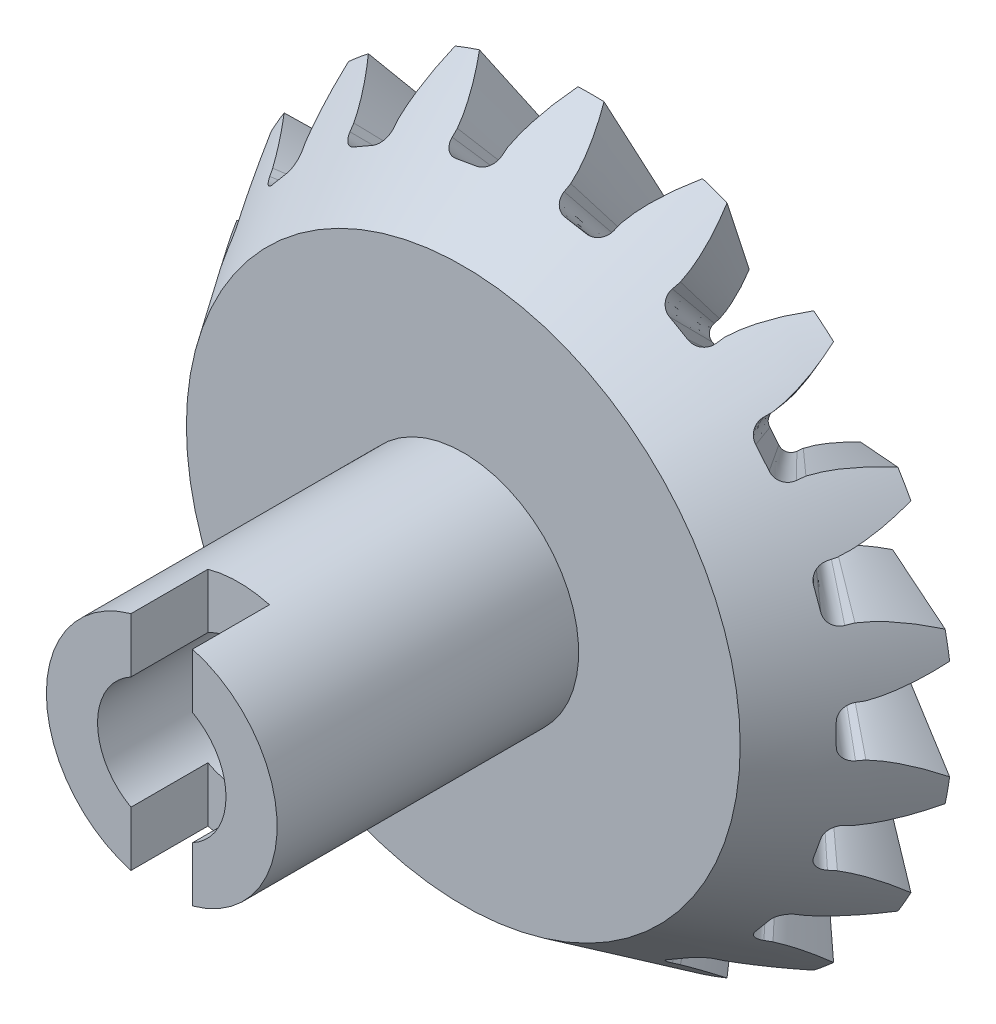
SolidWorks part; units mm, degrees
ref_plane "Front Plane" through (0, 0, 0) normal (0, 0, 1) x (1, 0, 0)
ref_plane "Top Plane" through (0, 0, 0) normal (0, 1, 0) x (1, 0, 0)
ref_plane "Right Plane" through (0, 0, 0) normal (1, 0, 0) x (0, 0, -1)
ref_axis "Gear Axis" through (0, 0, -1.3521) along (0, 0, 1)
sketch "Blank Sketch" plane through (0, 0, 0) normal (0, 1, 0) x (1, 0, 0)
  line L0 (0, 0) -> (0, -27.0416) construction
  line L1 (0, 0) -> (22.5, -15) construction
  line L2 (0, 0) -> (15.0115, -10.0077) construction
  line L3 (11.176, -15.7611) -> (15.6135, -9.1047)
  line L4 (15.6135, -9.1047) -> (23.5324, -13.4515)
  line L5 (23.5324, -13.4515) -> (17.9981, -21.7528)
  line L6 (17.9981, -21.7528) -> (4.175, -21.7528)
  line L7 (4.175, -21.7528) -> (4.175, -15.7611)
  line L8 (4.175, -15.7611) -> (11.176, -15.7611)
  line L9 (22.5, -15) -> (23.5324, -13.4515) construction
  line L10 (22.5, -15) -> (17.9981, -21.7528) construction
  line L11 (15.0115, -10.0077) -> (11.176, -15.7611) construction
  dimension "Axis" = 27.0416
  dimension "Cone" = 56.31
  dimension "Heel" = 27.0416
  dimension "Toe Cone" = 56.31
  dimension "Toe" = 18.0416
  dimension "Heel Square" = 90
  dimension "Addendum" = 1.8611
  dimension "Root Square" = 90
  dimension "Heel Rim" = 8.1158
  dimension "Toe Square" = 90
  dimension "Toe Rim" = 6.9147
  dimension "Front Square" = 90
  dimension "Face" = 4.927
  dimension "Back" = 13.8231
  dimension "Front" = 7.001
revolve "Blank" add sketch "Blank Sketch" angle 360 about L0
sketch "Cone Sketch" plane through (0, 0, 0) normal (0, 1, 0) x (1, 0, 0)
  line L0 (0, 0) -> (0, -27.0416) construction
  line L1 (0, 0) -> (24.5801, -16.3868)
  line L2 (0, 0) -> (12.9314, -8.6209)
  dimension "Axis" = 27.0416
  dimension "Toe Cone" = 56.31
  dimension "Heel Cone" = 56.31
  dimension "Heel" = 29.5416
  dimension "Toe" = 15.5416
ref_plane "Heel Plane" through (24.5801, 0, 16.3868) normal (0.8321, 0, 0.5547) x (0.5547, 0, -0.8321)
ref_plane "Toe Plane" through (12.9314, 0, 8.6209) normal (0.8321, 0, 0.5547) x (0.5547, 0, -0.8321)
sketch "Heel Section Sketch" plane through (24.5801, 0, 16.3868) normal (0.8321, 0, 0.5547) x (0.5547, 0, -0.8321)
  line L0 (0, 0) -> (-44.3125, 0) construction
  line L1 (-2.4254, 1.822) -> (-2.9568, 1.7989)
  line L2 (-2.4254, -1.822) -> (-2.9568, -1.7989)
  line L3 (4.4731, 5.3382) -> (4.4731, -5.3382)
  arc A0 (-2.9568, 1.7989) -> (-3.9494, 0.7429) centre (-2.9117, 0.762) ccw
  arc A1 (-3.9494, -0.7429) -> (-2.9568, -1.7989) centre (-2.9117, -0.762) ccw
  arc A2 (-3.9494, -0.7429) -> (-3.9494, 0.7429) centre (-44.3125, 0) ccw
  spline S0 degree 4 poles (-2.6185, 1.7952) (-2.5735, 1.8001) (-2.4634, 1.8153) (-2.3826, 1.8283) (-2.1666, 1.8686) (-2.0036, 1.9057) (-1.7812, 1.9593) (-1.5664, 2.0195) (-1.329, 2.0902) (-1.1027, 2.1645) (-0.8722, 2.2444) (-0.6468, 2.3281) (-0.412, 2.4198) (-0.1247, 2.538) (0.217, 2.6881) (0.607, 2.871) (1.0408, 3.0905) (1.4634, 3.3174) (1.8882, 3.5612) (2.2942, 3.8046) (2.7157, 4.0742) (3.0965, 4.325) (3.5292, 4.6295) (3.8609, 4.867) (4.3217, 5.2186) (4.5362, 5.3868) (4.8006, 5.5995) (4.951, 5.7231) (5.0219, 5.782) (5.0608, 5.8144) (5.0806, 5.831) knots 0 0 0 0 0 0.022117 0.039787 0.058126 0.081614 0.109122 0.13663 0.164138 0.191645 0.219153 0.246661 0.274169 0.305931 0.360947 0.415962 0.470978 0.525993 0.581009 0.636024 0.69104 0.746055 0.801071 0.856086 0.911102 0.955551 0.977775 0.988888 1 1 1 1 1 construction
  spline S1 degree 4 poles (-2.4254, 1.822) (-2.3913, 1.8275) (-2.324, 1.8392) (-2.1666, 1.8686) (-2.0036, 1.9057) (-1.7812, 1.9593) (-1.5664, 2.0195) (-1.329, 2.0902) (-1.1027, 2.1645) (-0.8722, 2.2444) (-0.6468, 2.3281) (-0.412, 2.4198) (-0.1247, 2.538) (0.217, 2.6881) (0.607, 2.871) (1.0408, 3.0905) (1.4634, 3.3174) (1.8882, 3.5612) (2.2942, 3.8046) (2.7157, 4.0742) (3.0965, 4.325) (3.5292, 4.6295) (3.8609, 4.867) (4.2239, 5.144) (4.3887, 5.2717) (4.4731, 5.3382) knots 0.022117 0.022117 0.022117 0.022117 0.022117 0.039787 0.058126 0.081614 0.109122 0.13663 0.164138 0.191645 0.219153 0.246661 0.274169 0.305931 0.360947 0.415962 0.470978 0.525993 0.581009 0.636024 0.69104 0.746055 0.801071 0.856086 0.911102 0.911102 0.911102 0.911102 0.911102
  spline S2 degree 4 poles (-2.6185, -1.7952) (-2.5735, -1.8001) (-2.4634, -1.8153) (-2.3826, -1.8283) (-2.1666, -1.8686) (-2.0036, -1.9057) (-1.7812, -1.9593) (-1.5664, -2.0195) (-1.329, -2.0902) (-1.1027, -2.1645) (-0.8722, -2.2444) (-0.6468, -2.3281) (-0.412, -2.4198) (-0.1247, -2.538) (0.217, -2.6881) (0.607, -2.871) (1.0408, -3.0905) (1.4634, -3.3174) (1.8882, -3.5612) (2.2942, -3.8046) (2.7157, -4.0742) (3.0965, -4.325) (3.5292, -4.6295) (3.8609, -4.867) (4.3217, -5.2186) (4.5362, -5.3868) (4.8006, -5.5995) (4.951, -5.7231) (5.0219, -5.782) (5.0608, -5.8144) (5.0806, -5.831) knots 0 0 0 0 0 0.022117 0.039787 0.058126 0.081614 0.109122 0.13663 0.164138 0.191645 0.219153 0.246661 0.274169 0.305931 0.360947 0.415962 0.470978 0.525993 0.581009 0.636024 0.69104 0.746055 0.801071 0.856086 0.911102 0.955551 0.977775 0.988888 1 1 1 1 1 construction
  spline S3 degree 4 poles (-2.4254, -1.822) (-2.3913, -1.8275) (-2.324, -1.8392) (-2.1666, -1.8686) (-2.0036, -1.9057) (-1.7812, -1.9593) (-1.5664, -2.0195) (-1.329, -2.0902) (-1.1027, -2.1645) (-0.8722, -2.2444) (-0.6468, -2.3281) (-0.412, -2.4198) (-0.1247, -2.538) (0.217, -2.6881) (0.607, -2.871) (1.0408, -3.0905) (1.4634, -3.3174) (1.8882, -3.5612) (2.2942, -3.8046) (2.7157, -4.0742) (3.0965, -4.325) (3.5292, -4.6295) (3.8609, -4.867) (4.2239, -5.144) (4.3887, -5.2717) (4.4731, -5.3382) knots 0.022117 0.022117 0.022117 0.022117 0.022117 0.039787 0.058126 0.081614 0.109122 0.13663 0.164138 0.191645 0.219153 0.246661 0.274169 0.305931 0.360947 0.415962 0.470978 0.525993 0.581009 0.636024 0.69104 0.746055 0.801071 0.856086 0.911102 0.911102 0.911102 0.911102 0.911102
  dimension "Root" = 40.3699
  dimension "Fillet" = 1.0378
  dimension "Centre" = 44.3125
sketch "Toe Section Sketch" plane through (12.9314, 0, 8.6209) normal (0.8321, 0, 0.5547) x (0.5547, 0, -0.8321)
  line L0 (0, 0) -> (-23.3125, 0) construction
  line L1 (-1.276, 0.9585) -> (-1.5556, 0.9464)
  line L2 (-1.276, -0.9585) -> (-1.5556, -0.9464)
  line L3 (2.3533, 2.8084) -> (2.3533, -2.8084)
  arc A0 (-1.5556, 0.9464) -> (-2.0777, 0.3908) centre (-1.5318, 0.4009) ccw
  arc A1 (-2.0777, -0.3908) -> (-1.5556, -0.9464) centre (-1.5318, -0.4009) ccw
  arc A2 (-2.0777, -0.3908) -> (-2.0777, 0.3908) centre (-23.3125, 0) ccw
  spline S0 degree 4 poles (-1.3801, 0.944) (-1.3498, 0.9477) (-1.2981, 0.9547) (-1.2515, 0.9622) (-1.1417, 0.9827) (-1.0525, 1.0029) (-0.9382, 1.0306) (-0.8233, 1.0626) (-0.6997, 1.0996) (-0.5798, 1.1388) (-0.459, 1.1807) (-0.3402, 1.2248) (-0.2168, 1.273) (-0.0656, 1.3353) (0.1141, 1.4142) (0.3193, 1.5104) (0.5475, 1.6259) (0.7699, 1.7453) (0.9934, 1.8735) (1.207, 2.0016) (1.4287, 2.1434) (1.6291, 2.2754) (1.8566, 2.4355) (2.0313, 2.5606) (2.2734, 2.7453) (2.4008, 2.8452) (2.5617, 2.975) (2.632, 3.0335) (2.6721, 3.067) knots 0 0 0 0 0 0.022117 0.039787 0.058126 0.081614 0.109122 0.13663 0.164138 0.191645 0.219153 0.246661 0.274169 0.305931 0.360947 0.415962 0.470978 0.525993 0.581009 0.636024 0.69104 0.746055 0.801071 0.856086 0.911102 0.955551 1 1 1 1 1 construction
  spline S1 degree 4 poles (-1.276, 0.9585) (-1.2581, 0.9614) (-1.2218, 0.9678) (-1.1417, 0.9827) (-1.0525, 1.0029) (-0.9382, 1.0306) (-0.8233, 1.0626) (-0.6997, 1.0996) (-0.5798, 1.1388) (-0.459, 1.1807) (-0.3402, 1.2248) (-0.2168, 1.273) (-0.0656, 1.3353) (0.1141, 1.4142) (0.3193, 1.5104) (0.5475, 1.6259) (0.7699, 1.7453) (0.9934, 1.8735) (1.207, 2.0016) (1.4287, 2.1434) (1.6291, 2.2754) (1.8566, 2.4355) (2.0313, 2.5606) (2.2221, 2.7061) (2.3088, 2.7734) (2.3533, 2.8084) knots 0.022117 0.022117 0.022117 0.022117 0.022117 0.039787 0.058126 0.081614 0.109122 0.13663 0.164138 0.191645 0.219153 0.246661 0.274169 0.305931 0.360947 0.415962 0.470978 0.525993 0.581009 0.636024 0.69104 0.746055 0.801071 0.856086 0.911102 0.911102 0.911102 0.911102 0.911102
  spline S2 degree 4 poles (-1.3801, -0.944) (-1.3498, -0.9477) (-1.2981, -0.9547) (-1.2515, -0.9622) (-1.1417, -0.9827) (-1.0525, -1.0029) (-0.9382, -1.0306) (-0.8233, -1.0626) (-0.6997, -1.0996) (-0.5798, -1.1388) (-0.459, -1.1807) (-0.3402, -1.2248) (-0.2168, -1.273) (-0.0656, -1.3353) (0.1141, -1.4142) (0.3193, -1.5104) (0.5475, -1.6259) (0.7699, -1.7453) (0.9934, -1.8735) (1.207, -2.0016) (1.4287, -2.1434) (1.6291, -2.2754) (1.8566, -2.4355) (2.0313, -2.5606) (2.2734, -2.7453) (2.4008, -2.8452) (2.5617, -2.975) (2.632, -3.0335) (2.6721, -3.067) knots 0 0 0 0 0 0.022117 0.039787 0.058126 0.081614 0.109122 0.13663 0.164138 0.191645 0.219153 0.246661 0.274169 0.305931 0.360947 0.415962 0.470978 0.525993 0.581009 0.636024 0.69104 0.746055 0.801071 0.856086 0.911102 0.955551 1 1 1 1 1 construction
  spline S3 degree 4 poles (-1.276, -0.9585) (-1.2581, -0.9614) (-1.2218, -0.9678) (-1.1417, -0.9827) (-1.0525, -1.0029) (-0.9382, -1.0306) (-0.8233, -1.0626) (-0.6997, -1.0996) (-0.5798, -1.1388) (-0.459, -1.1807) (-0.3402, -1.2248) (-0.2168, -1.273) (-0.0656, -1.3353) (0.1141, -1.4142) (0.3193, -1.5104) (0.5475, -1.6259) (0.7699, -1.7453) (0.9934, -1.8735) (1.207, -2.0016) (1.4287, -2.1434) (1.6291, -2.2754) (1.8566, -2.4355) (2.0313, -2.5606) (2.2221, -2.7061) (2.3088, -2.7734) (2.3533, -2.8084) knots 0.022117 0.022117 0.022117 0.022117 0.022117 0.039787 0.058126 0.081614 0.109122 0.13663 0.164138 0.191645 0.219153 0.246661 0.274169 0.305931 0.360947 0.415962 0.470978 0.525993 0.581009 0.636024 0.69104 0.746055 0.801071 0.856086 0.911102 0.911102 0.911102 0.911102 0.911102
  dimension "Root" = 21.2383
  dimension "Fillet" = 0.546
  dimension "Centre" = 23.3125
loft "Tooth Space" cut profiles "Heel Section Sketch", "Toe Section Sketch"
pattern_circular "Teeth" count 18 over 360 about axis through (0, 0, -1.3521) along (0, 0, 1) of "Tooth Space"
sketch "Sketch1" plane through (0, 0, 21.7528) normal (0, 0, 1) x (1, 0, 0)
  circle A0 centre (0, 0) radius 4.175
  circle A1 centre (0, 0) radius 7.5
  dimension "D1" = 15
  dimension "D2" = 8.35
extrude "Boss-Extrude1" add sketch "Sketch1" along normal up to vertex (14.5972 mm away)
sketch "Sketch2" plane through (0, 0, 36.35) normal (0, 0, 1) x (1, 0, 0)
  line L0 (2, -7.2284) -> (2, -3.6648)
  line L1 (-2, 7.2284) -> (-2, 3.6648)
  line L2 (-2, 3.6648) -> (-2, -3.6648) construction
  line L3 (-2, -3.6648) -> (-2, -7.2284)
  line L4 (2, -3.6648) -> (2, 3.6648) construction
  line L5 (2, 3.6648) -> (2, 7.2284)
  circle A0 centre (0, 0) radius 7.5 construction
  arc A1 (-2, 7.2284) -> (-2, -7.2284) centre (0, 0) ccw
  arc A2 (2, 7.2284) -> (-2, 7.2284) centre (0, 0) ccw construction
  arc A3 (-2, -7.2284) -> (2, -7.2284) centre (0, 0) ccw construction
  arc A4 (2, -7.2284) -> (2, 7.2284) centre (0, 0) ccw
  arc A5 (-2, 3.6648) -> (-2, -3.6648) centre (0, 0) ccw
  arc A6 (2, 3.6648) -> (-2, 3.6648) centre (0, 0) ccw construction
  arc A7 (-2, -3.6648) -> (2, -3.6648) centre (0, 0) ccw construction
  arc A8 (2, -3.6648) -> (2, 3.6648) centre (0, 0) ccw
  dimension "D2" = 8.35
  dimension "D1" = 2
  dimension "2" = 2
extrude "Boss-Extrude2" add sketch "Sketch2" along normal blind 5
equation "\"No. of Teeth\"= 18"
equation "\"Module\"= 2.5"
equation "\"Bore Diameter\"= 8.35"
equation "\"Pressure Angle\"= 20"
equation "\"Shaft Angle\"= 90"
equation "\"Mate Teeth\"= 12"
equation "\"Pitch Cone Angle\"= IIF ( ( \"Mate Teeth\" / \"No. of Teeth\" + cos ( \"Shaft Angle\" ) ) > 0 , atn ( sin ( \"Shaft Angle\" ) / ( \"Mate Teeth\" / \"No. of Teeth\" + cos ( \"Shaft Angle\" ) ) ) , 180 + atn ( sin ( \"Shaft Angle\" ) / ( \"Mate Teeth\" / \"No. of Teeth\" + cos ( \"Shaft Angle\" ) ) ) )"
equation "\"Mate Cone Angle\"= \"Shaft Angle\" - \"Pitch Cone Angle\""
equation "\"Addendum\"= IIF ( \"No. of Teeth\" >= \"Mate Teeth\" , 0.54 * \"Module\" + 0.46 * \"Module\" / ( ( \"No. of Teeth\" * cos ( \"Mate Cone Angle\" ) ) / ( \"Mate Teeth\" * cos ( \"Pitch Cone Angle\" ) ) ) , 2 * \"Module\" - ( 0.54 * \"Module\" + 0.46 * \"Module\" / ( ( \"Mate Teeth\" * cos ( \"Pitch Cone Angle\" ) ) / ( \"No. of Teeth\" * cos ( \"Mate Cone Angle\" ) ) ) ) )"
equation "\"Outer Diameter\"= \"No. of Teeth\" * \"Module\" + 2 * \"Addendum\" * cos ( \"Pitch Cone Angle\" )"
equation "\"Pitch Diameter\"= \"No. of Teeth\" * \"Module\""
equation "\"Backlash\"= IIF ( \"Module\" <= 1 , 0.3 * \"Module\" , 0.3 )"
equation "\"Arc Length\"= ( ( \"Module\" * pi ) / 2 + \"Backlash\" - 2 * ( \"Addendum\" - \"Module\" ) * tan ( \"Pressure Angle\" ) )"
equation "\"Fillet Radius\"= 0.38 * \"Module\""
equation "\"Mate Addendum\"= 2 * \"Module\" - \"Addendum\""
equation "\"Dedendum\"= 2.188 * \"Module\" - \"Addendum\""
equation "\"Tooth Depth\"= \"Addendum\" + \"Dedendum\""
equation "\"Mate Dedendum\"= 2.188 * \"Module\" - \"Mate Addendum\""
equation "\"Face Width\"= 9"
equation "\"Cone Distance\"= \"Pitch Diameter\" / ( 2 * sin ( \"Pitch Cone Angle\" ) )"
equation "\"Dedendum Angle\"= atn ( \"Dedendum\" / \"Cone Distance\" )"
equation "\"Mate Dedendum Angle\"= atn ( \"Mate Dedendum\" / \"Cone Distance\" )"
equation "\"Face Angle\"= \"Pitch Cone Angle\" + \"Mate Dedendum Angle\""
equation "\"Root Angle\"= \"Pitch Cone Angle\" - \"Dedendum Angle\""
equation "\"Overrun\"= \"Module\""
equation "\"Back Cone Pitch Diameter\"= \"Pitch Diameter\" / cos ( \"Pitch Cone Angle\" )"
equation "\"Back Cone Outer Diameter\"= \"Back Cone Pitch Diameter\" + 2 * \"Addendum\""
equation "\"Root Diameter\"= \"Back Cone Outer Diameter\" - 2 * \"Tooth Depth\""
equation "\"Base Diameter\"= \"Back Cone Pitch Diameter\" * cos ( \"Pressure Angle\" )"
equation "\"Base Radius\"= \"Base Diameter\" / 2"
equation "\"Tooth Thickness\"= \"Module\" * pi - \"Arc Length\""
equation "\"Half Space Angle\"= ( \"Arc Length\" / \"Back Cone Pitch Diameter\" ) * 180 / pi"
equation "\"Involute Fn\"= tan ( \"Pressure Angle\" ) - \"Pressure Angle\" * pi / 180"
equation "\"Flank Offset\"= \"Arc Length\" / \"Back Cone Pitch Diameter\" - \"Involute Fn\""
equation "\"Tip Cap Diameter\"= \"Back Cone Outer Diameter\" + 2 * \"Module\""
equation "\"Flank Start Diameter\"= IIF ( \"Base Diameter\" >= ( \"Root Diameter\" + 3 * \"Fillet Radius\" ) , \"Base Diameter\" , \"Root Diameter\" + 3 * \"Fillet Radius\" )"
equation "\"Involute t1\"= ( abs ( ( \"Flank Start Diameter\" / \"Base Diameter\" ) ^ 2 - 1 ) ) ^ 0.5"
equation "\"Involute t2\"= ( abs ( ( \"Tip Cap Diameter\" / \"Base Diameter\" ) ^ 2 - 1 ) ) ^ 0.5"
equation "\"Flank Arc Radius\"= ( \"Back Cone Pitch Diameter\" / 2 ) * sin ( \"Pressure Angle\" )"
equation "\"Flank Centre Angle\"= \"Half Space Angle\" + \"Pressure Angle\""
equation "\"Heel Distance\"= \"Cone Distance\" + \"Overrun\""
equation "\"Toe Distance\"= \"Cone Distance\" - \"Face Width\" - \"Overrun\""
equation "\"Heel Scale\"= \"Heel Distance\" / \"Cone Distance\""
equation "\"Toe Scale\"= \"Toe Distance\" / \"Cone Distance\""
equation "\"Heel Virtual Radius\"= \"Heel Distance\" * tan ( \"Pitch Cone Angle\" )"
equation "\"Toe Virtual Radius\"= \"Toe Distance\" * tan ( \"Pitch Cone Angle\" )"
equation "\"Axis@Blank Sketch\"= \"Cone Distance\""
equation "\"Cone@Blank Sketch\"= \"Pitch Cone Angle\""
equation "\"Heel@Blank Sketch\"= \"Cone Distance\""
equation "\"Toe Cone@Blank Sketch\"= \"Pitch Cone Angle\""
equation "\"Toe@Blank Sketch\"= \"Cone Distance\" - \"Face Width\""
equation "\"Addendum@Blank Sketch\"= \"Addendum\""
equation "\"Heel Rim@Blank Sketch\"= \"Dedendum\" + \"Module\" / cos ( \"Pitch Cone Angle\" )"
equation "\"Toe Rim@Blank Sketch\"= \"Dedendum\" - \"Face Width\" * tan ( \"Dedendum Angle\" ) + \"Module\" / cos ( \"Pitch Cone Angle\" )"
equation "\"Face@Blank Sketch\"= \"Mate Dedendum Angle\""
equation "\"Back@Blank Sketch\"= \"Cone Distance\" * sin ( \"Pitch Cone Angle\" ) - \"Dedendum\" * cos ( \"Pitch Cone Angle\" ) - \"Module\" - \"Bore Diameter\" / 2"
equation "\"Front@Blank Sketch\"= ( \"Cone Distance\" - \"Face Width\" ) * sin ( \"Pitch Cone Angle\" ) - ( \"Dedendum\" - \"Face Width\" * tan ( \"Dedendum Angle\" ) + \"Module\" / cos ( \"Pitch Cone Angle\" ) ) * cos ( \"Pitch Cone Angle\" ) - \"Bore Diameter\" / 2"
equation "\"Axis@Cone Sketch\"= \"Cone Distance\""
equation "\"Heel Cone@Cone Sketch\"= \"Pitch Cone Angle\""
equation "\"Heel@Cone Sketch\"= \"Heel Distance\""
equation "\"Toe Cone@Cone Sketch\"= \"Pitch Cone Angle\""
equation "\"Toe@Cone Sketch\"= \"Toe Distance\""
equation "\"Centre@Heel Section Sketch\"= \"Heel Virtual Radius\""
equation "\"Root@Heel Section Sketch\"= ( \"Root Diameter\" / 2 ) * \"Heel Scale\""
equation "\"Fillet@Heel Section Sketch\"= ( \"Fillet Radius\" ) * \"Heel Scale\""
equation "\"Centre@Toe Section Sketch\"= \"Toe Virtual Radius\""
equation "\"Root@Toe Section Sketch\"= ( \"Root Diameter\" / 2 ) * \"Toe Scale\""
equation "\"Fillet@Toe Section Sketch\"= ( \"Fillet Radius\" ) * \"Toe Scale\""
equation "\"Count@Teeth\"= \"No. of Teeth\""
